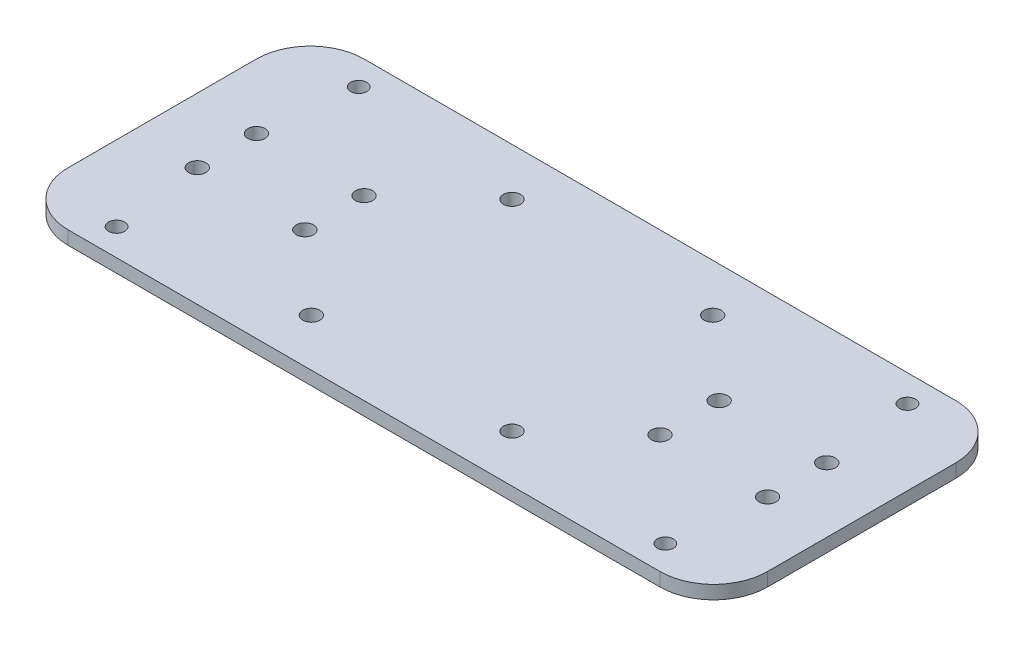
SolidWorks part; units mm, degrees
ref_plane "Front Plane" through (0, 0, 0) normal (0, 0, 1) x (1, 0, 0)
ref_plane "Top Plane" through (0, 0, 0) normal (0, 1, 0) x (1, 0, 0)
ref_plane "Right Plane" through (0, 0, 0) normal (1, 0, 0) x (0, 0, -1)
sketch "Sketch1" plane through (0, 0, 0) normal (0, 1, 0) x (1, 0, 0)
  line L1 (10, 0) -> (120, 0)
  line L2 (0, 10) -> (0, 45)
  line L3 (10, 55) -> (120, 55)
  line L4 (130, 10) -> (130, 45)
  arc A0 (10, 55) -> (0, 45) centre (10, 45) ccw
  arc A1 (0, 10) -> (10, 0) centre (10, 10) ccw
  arc A2 (130, 10) -> (120, 0) centre (120, 10) cw
  arc A3 (120, 55) -> (130, 45) centre (120, 45) cw
  point P7 (0, 55)
  point P10 (0, 0)
  point P13 (130, 0)
  dimension "D3" = 10
  dimension "D4" = 10
  dimension "D5" = 10
  dimension "D6" = 10
  dimension "D1" = 130
  dimension "D2" = 55
extrude "Boss-Extrude1" add sketch "Sketch1" along normal blind 2.5
sketch "Sketch2" plane through (0, 2.5, 0) normal (0, 1, 0) x (1, 0, 0)
  line L0 (0, 45) -> (0, 10) construction
  line L1 (10, 0) -> (120, 0) construction
  line L2 (120, 55) -> (10, 55) construction
  line L3 (65, 55) -> (65, 0) construction
  circle A0 centre (14, 5) radius 1.5
  circle A1 centre (14, 50) radius 1.5
  circle A2 centre (116, 5) radius 1.5
  circle A3 centre (116, 50) radius 1.5
  dimension "D1" = 3
  dimension "D4" = 3
  dimension "D2" = 14
  dimension "D3" = 5
  dimension "D5" = 5
extrude "Cut-Extrude1" cut sketch "Sketch2" against normal through all
sketch "Sketch3" plane through (0, 2.5, 0) normal (0, 1, 0) x (1, 0, 0)
  circle A0 centre (12, 33) radius 1.6
extrude "Cut-Extrude2" cut sketch "Sketch3" against normal blind 10
sketch "Sketch4" plane through (0, 2.5, 0) normal (0, 1, 0) x (1, 0, 0)
  circle A0 centre (12, 22) radius 1.6
extrude "Cut-Extrude3" cut sketch "Sketch4" against normal blind 10
sketch "Sketch5" plane through (0, 2.5, 0) normal (0, 1, 0) x (1, 0, 0)
  circle A0 centre (32, 33) radius 1.6
  circle A1 centre (32, 22) radius 1.6
extrude "Cut-Extrude4" cut sketch "Sketch5" against normal blind 10 contours A0 | A1
sketch "Sketch8" plane through (0, 2.5, 0) normal (0, 1, 0) x (1, 0, 0)
  circle A0 centre (98, 33) radius 1.6
  circle A1 centre (98, 22) radius 1.6
  circle A2 centre (118, 33) radius 1.6
  circle A3 centre (118, 22) radius 1.6
extrude "Cut-Extrude5" cut sketch "Sketch8" against normal blind 10
sketch "Sketch9" plane through (0, 2.5, 0) normal (0, 1, 0) x (1, 0, 0)
  circle A0 centre (46.35, 46.15) radius 1.6
  circle A1 centre (83.65, 46.15) radius 1.6
  circle A2 centre (83.65, 8.85) radius 1.6
  circle A3 centre (46.35, 8.85) radius 1.6
extrude "Cut-Extrude6" cut sketch "Sketch9" against normal blind 10
